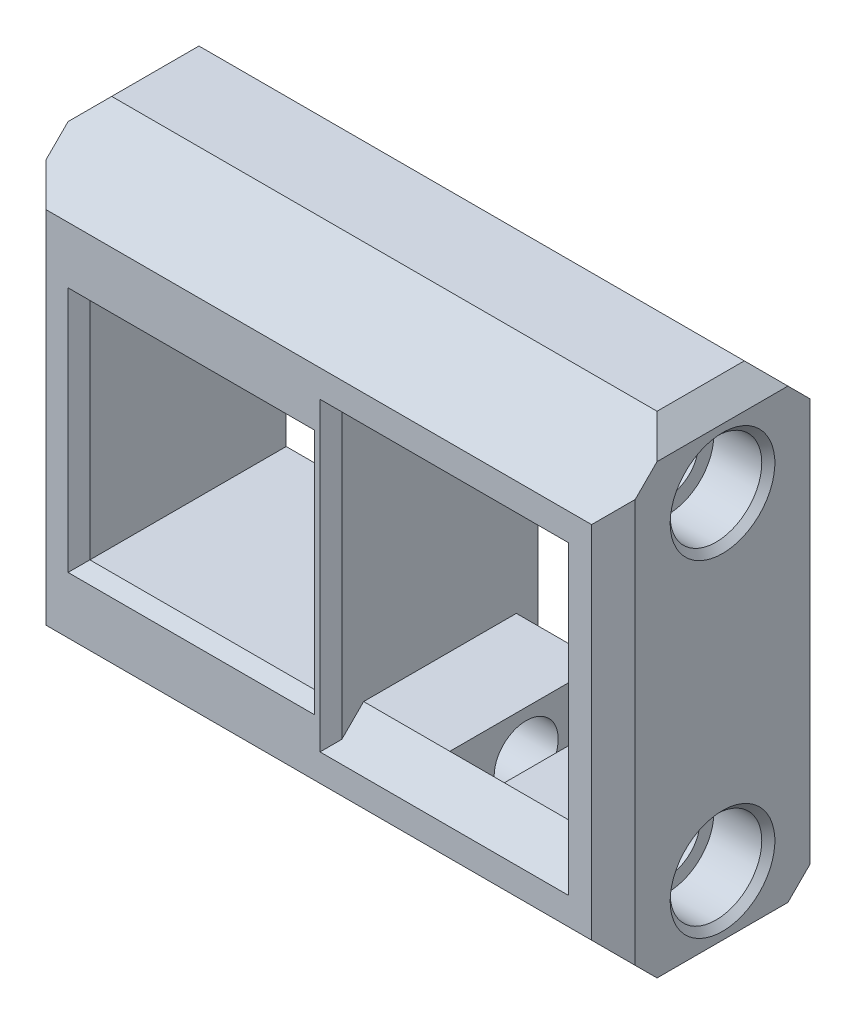
SolidWorks part; units mm, degrees
ref_plane "Front Plane" through (0, 0, 0) normal (0, 0, 1) x (1, 0, 0)
ref_plane "Top Plane" through (0, 0, 0) normal (0, 1, 0) x (1, 0, 0)
ref_plane "Right Plane" through (0, 0, 0) normal (1, 0, 0) x (0, 0, -1)
sketch "Sketch1" plane through (0, 0, 0) normal (0, 0, 1) x (1, 0, 0)
  line L1 (0, 0) -> (68.58, 0)
  line L2 (0, 0) -> (0, 57.15)
  line L3 (0, 57.15) -> (68.58, 57.15)
  line L4 (68.58, 0) -> (68.58, 57.15)
  dimension "D1" = 57.15
  dimension "D2" = 68.58
extrude "Boss-Extrude1" add sketch "Sketch1" along normal blind 25.4
sketch "Sketch2" plane through (0, 0, 25.4) normal (0, 0, 1) x (1, 0, 0)
  line L1 (6.35, 15.494) -> (32.512, 15.494)
  line L2 (6.35, 15.494) -> (6.35, 41.656)
  line L3 (6.35, 41.656) -> (32.512, 41.656)
  line L4 (32.512, 15.494) -> (32.512, 41.656)
  line L5 (35.687, 42.545) -> (62.103, 42.545)
  line L6 (35.687, 42.545) -> (35.687, 14.605)
  line L7 (35.687, 14.605) -> (62.103, 14.605)
  line L8 (62.103, 42.545) -> (62.103, 14.605)
  line L9 (82.1588, 28.575) -> (-8.3557, 28.575) construction
  line L10 (68.58, 57.15) -> (0, 57.15) construction
  line L12 (0, 57.15) -> (0, 0) construction
  point P10 (6.35, 28.575)
  point P13 (62.103, 28.575)
  dimension "D1" = 26.162
  dimension "D2" = 27.94
  dimension "D3" = 3.175
  dimension "D4" = 28.575
  dimension "D5" = 6.35
  dimension "D6" = 26.416
extrude "Cut-Extrude1" cut sketch "Sketch2" against normal through all
sketch "Sketch5" plane through (68.58, 0, 0) normal (1, 0, 0) x (0, 0, -1)
  line L0 (-25.4, 57.15) -> (0, 57.15) construction
  line L1 (-40.1188, 28.575) -> (12.2247, 28.575) construction
  line L3 (0, 0) -> (0, 57.15) construction
  circle A0 centre (-12.7, 47.625) radius 3.556
  circle A1 centre (-12.7, 9.525) radius 3.7293
  point P5 (0, 0)
  point P10 (0, 0)
  point P11 (0, 0)
  dimension "D1" = 7.112
  dimension "D2" = 19.05
  dimension "D3" = 28.575
  dimension "D4" = 38.1
  dimension "D5" = 12.7
extrude "Cut-Extrude2" cut sketch "Sketch5" against normal through all contours A0 | A1 region at (68.58, 47.625, 12.7) region at (68.58, 9.525, 12.7)
sketch "Sketch6" plane through (68.58, 0, 0) normal (1, 0, 0) x (0, 0, -1)
  line L0 (-21.59, 47.625) -> (-21.59, 12.2127)
  line L1 (-3.81, 47.625) -> (-3.81, 6.8373)
  arc A0 (-21.59, 47.625) -> (-3.81, 47.625) centre (-12.7, 47.625) cw
  arc A2 (-3.81, 6.8373) -> (-21.59, 12.2127) centre (-12.7, 9.525) cw
  dimension "D1" = 8.89
extrude "Cut-Extrude3" cut sketch "Sketch6" against normal blind 6.35 from offset 16.51 offset against normal yes
chamfer "Chamfer1" distance 1.27 angle 45 12 edges at (62.103, 28.575, 25.4) (35.687, 28.575, 25.4) (6.35, 28.575, 25.4) (19.431, 15.494, 25.4) (32.512, 28.575, 25.4) (19.431, 41.656, 25.4) (62.103, 28.575, 0) (35.687, 28.575, 0) (19.431, 15.494, 0) (6.35, 28.575, 0) (32.512, 28.575, 0) (19.431, 41.656, 0)
chamfer "Chamfer2" distance 2.54 angle 45 8 edges at (0, 0, 12.7) (0, 28.575, 0) (0, 57.15, 12.7) (0, 28.575, 25.4) (68.58, 0, 12.7) (68.58, 28.575, 25.4) (68.58, 57.15, 12.7) (68.58, 28.575, 0)
chamfer "Chamfer3" distance 7.62 angle 45 4 edges at (34.29, 0, 0) (34.29, 0, 25.4) (34.29, 57.15, 0) (34.29, 57.15, 25.4)
sketch "Sketch7" plane through (68.58, 0, 0) normal (1, 0, 0) x (0, 0, -1)
  circle A0 centre (-12.7, 47.625) radius 5.334
  circle A1 centre (-12.7, 9.525) radius 5.334
  dimension "D1" = 10.668
extrude "Cut-Extrude4" cut sketch "Sketch7" against normal blind 6.35
sketch "Sketch9" plane through (0, 0, 0) normal (-1, 0, 0) x (0, 0, 1)
  line L1 (16.0729, 53.467) -> (9.3271, 53.467)
  line L2 (9.3271, 53.467) -> (5.9542, 47.625)
  line L3 (5.9542, 47.625) -> (9.3271, 41.783)
  line L4 (9.3271, 41.783) -> (16.0729, 41.783)
  line L5 (16.0729, 41.783) -> (19.4458, 47.625)
  line L6 (19.4458, 47.625) -> (16.0729, 53.467)
  line L7 (16.0729, 15.367) -> (9.3271, 15.367)
  line L8 (9.3271, 15.367) -> (5.9542, 9.525)
  line L9 (5.9542, 9.525) -> (9.3271, 3.683)
  line L10 (9.3271, 3.683) -> (16.0729, 3.683)
  line L11 (16.0729, 3.683) -> (19.4458, 9.525)
  line L12 (19.4458, 9.525) -> (16.0729, 15.367)
  circle A0 centre (12.7, 47.625) radius 5.842 construction
  circle A1 centre (12.7, 9.525) radius 5.842 construction
  dimension "D1" = 11.684
extrude "Cut-Extrude5" cut sketch "Sketch9" against normal blind 7.62
chamfer "Chamfer4" distance 0.762 angle 45 14 edges at (68.58, 9.525, 7.366) (68.58, 47.625, 7.366) (0, 12.446, 17.7593) (0, 6.604, 17.7593) (0, 3.683, 12.7) (0, 6.604, 7.6407) (0, 12.446, 7.6407) (0, 15.367, 12.7) (0, 44.704, 7.6407) (0, 50.546, 7.6407) (0, 53.467, 12.7) (0, 50.546, 17.7593) (0, 44.704, 17.7593) (0, 41.783, 12.7)
chamfer "Chamfer5" distance 3.81 angle 45 4 edges at (48.895, 14.605, 0) (48.895, 42.545, 0) (48.895, 42.545, 25.4) (48.895, 14.605, 25.4)
